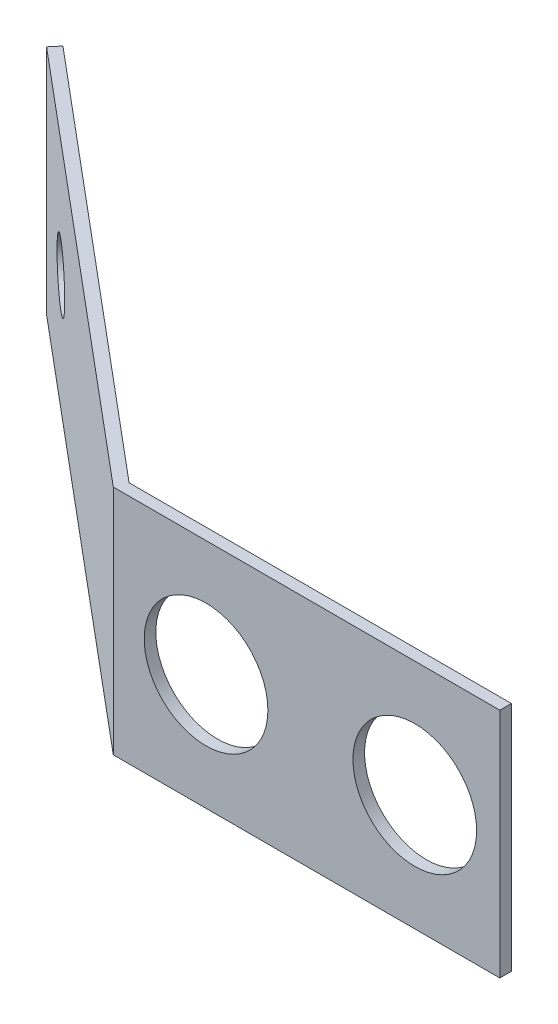
SolidWorks part; units mm, degrees
material "Perspex (TM) GS Acrylic Cast Sheet"
ref_plane "Front Plane" through (0, 0, 0) normal (0, 0, 1) x (1, 0, 0)
ref_plane "Top Plane" through (0, 0, 0) normal (0, 1, 0) x (1, 0, 0)
ref_plane "Right Plane" through (0, 0, 0) normal (1, 0, 0) x (0, 0, -1)
sketch "Sketch1" plane through (0, 0, 0) normal (0, 1, 0) x (1, 0, 0)
  line L0 (0, 0) -> (50, 0)
  line L1 (-16.5, 0) -> (16.5, 0) construction
  line L2 (0, 0) -> (-53.6231, 44.9951)
  dimension "D1" = 140
  dimension "D2" = 70
  dimension "D3" = 50
extrude "Extrude-Thin1" add sketch "Sketch1" along normal blind 30 thin thin type one direction wall 1.5
sketch "Sketch2" plane through (0, 0, 0) normal (-0.6428, 0, 0.766) x (0.766, 0, 0.6428)
  line L0 (-70, 30) -> (-70, 0) construction
  line L1 (30.023, 0) -> (-30.023, 0) construction
  circle A0 centre (-55, 15) radius 4
  dimension "D1" = 8
  dimension "D2" = 15
  dimension "D3" = 15
extrude "Cut-Extrude1" cut sketch "Sketch2" against normal blind 10
sketch "Sketch3" plane through (0, 0, 0) normal (0, 0, 1) x (1, 0, 0)
  line L1 (0, 30) -> (0, 0) construction
  line L2 (30.023, 0) -> (-30.023, 0) construction
  circle A0 centre (12, 15) radius 8
  circle A1 centre (39, 15) radius 8
  dimension "D1" = 16
  dimension "D2" = 27
  dimension "D3" = 12
  dimension "D4" = 15
extrude "Cut-Extrude2" cut sketch "Sketch3" against normal blind 10
